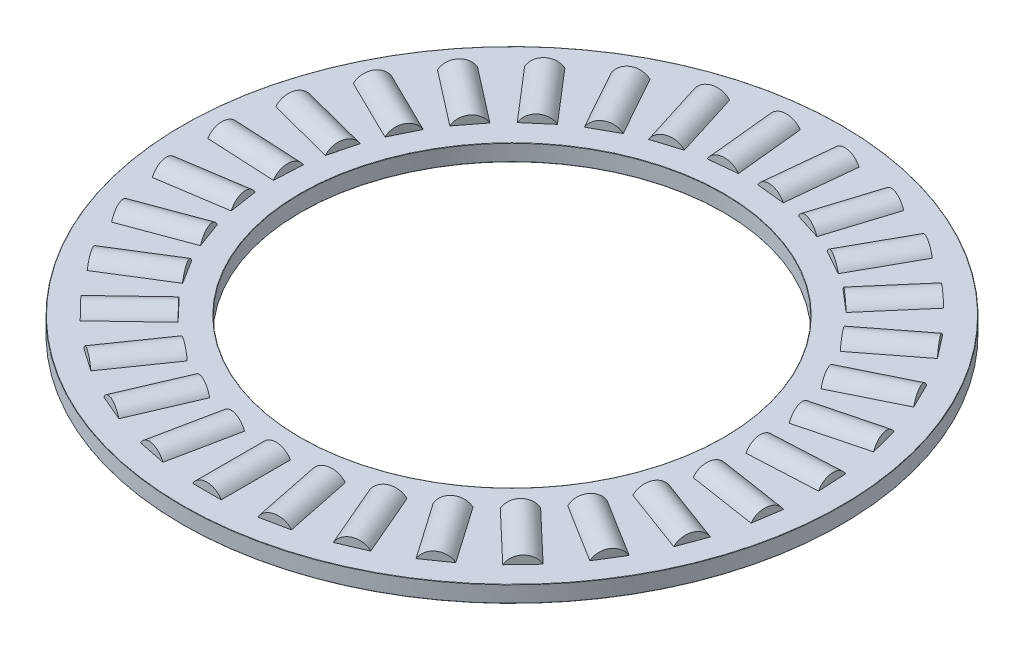
SolidWorks part; units mm, degrees
ref_plane "Front Plane" through (0, 0, 0) normal (0, 0, 1) x (1, 0, 0)
ref_plane "Top Plane" through (0, 0, 0) normal (0, 1, 0) x (1, 0, 0)
ref_plane "Right Plane" through (0, 0, 0) normal (1, 0, 0) x (0, 0, -1)
sketch "Sketch1" plane through (0, 0, 0) normal (1, 0, 0) x (0, 0, -1)
  line L0 (-19.8437, 0) -> (19.8438, 0) construction
  line L1 (0, -0.9922) -> (0, 0.9922) construction
  line L2 (-19.8438, 0.4961) -> (-12.7254, 0.4961)
  line L3 (-19.8438, 0.4961) -> (-19.8438, -0.4961)
  line L4 (-19.8438, -0.4961) -> (-12.7254, -0.4961)
  line L5 (-12.7254, 0.4961) -> (-12.7254, -0.4961)
  line L7 (-16.2846, 0.9922) -> (-16.2846, 0.4961) construction
  line L8 (-18.3682, 0.9922) -> (-14.201, 0.9922) construction
  line L9 (-18.3682, 0.9922) -> (-18.3682, -0.9922) construction
  line L10 (-18.3682, -0.9922) -> (-14.201, -0.9922) construction
  line L11 (-14.201, 0.9922) -> (-14.201, -0.9922) construction
  point P16 (-18.3682, 0)
  dimension "OD" = 39.6875
  dimension "Shaft Dia" = 25.4508
  dimension "Th" = 1.9844
  dimension "D2" = 0.9922
  dimension "D1" = 4.1672
  dimension "D3" = 7.1184
revolve "Revolve1" add sketch "Sketch1" angle 360 about L1
sketch "Sketch3" plane through (0, 0, 0) normal (1, 0, 0) x (0, 0, -1)
  line L0 (-18.3682, 0.9922) -> (-18.3682, -0.9922) construction
  line L1 (-18.3682, 0) -> (-14.201, 0)
  line L2 (-18.3682, 0) -> (-18.3682, 0.9922)
  line L3 (-18.3682, 0.9922) -> (-14.201, 0.9922)
  line L4 (-14.201, 0) -> (-14.201, 0.9922)
revolve "Cut-Revolve1" cut sketch "Sketch3" angle 360 about L1
sketch "Sketch2" plane through (0, 0, 0) normal (1, 0, 0) x (0, 0, -1)
  line L1 (-18.3682, 0) -> (-14.201, 0)
  line L2 (-18.3682, 0) -> (-18.3682, 0.9922)
  line L3 (-18.3682, 0.9922) -> (-14.201, 0.9922)
  line L4 (-14.201, 0) -> (-14.201, 0.9922)
revolve "Revolve2" add sketch "Sketch2" angle 360 about L1
ref_axis "Axis1" through (0, 0.9922, 0) along (0, -1, 0)
pattern_circular "CirPattern1" count 31 every 11.613 about axis through (0, 0.9922, 0) along (0, -1, 0) of bodies 187 411
pattern_circular "CirPattern2" count 31 every 11.613 about axis through (0, 0.9922, 0) along (0, -1, 0) of "Cut-Revolve1"
sketch "Sketch4" plane through (0, 0, 0) normal (1, 0, 0) x (0, 0, -1)
  line L0 (-19.8438, 0.4961) -> (-19.8438, -0.4961) construction
  line L1 (-11.9062, 9.1091) -> (-6.35, 9.1091)
  line L2 (-11.9062, 9.1091) -> (-11.9062, 9.9219)
  line L3 (-11.9062, 9.9219) -> (-6.35, 9.9219)
  line L4 (-6.35, 9.1091) -> (-6.35, 9.9219)
  line L5 (-11.9062, -9.9219) -> (-12.7254, -9.9219)
  line L6 (-11.9062, -9.9219) -> (-11.9062, -9.1091)
  line L7 (-11.9062, -9.1091) -> (-12.7254, -9.1091)
  line L8 (-12.7254, -9.9219) -> (-12.7254, -9.1091)
  line L10 (-12.7254, 0.4961) -> (-12.7254, -0.4961) construction
  line L11 (0, 0) -> (-19.8437, 0) construction
  line L12 (-19.8437, 0) -> (19.8438, 0) construction
  line L13 (0, -0.9922) -> (0, 0.9922) construction
  dimension "Ht" = 19.8438
  dimension "Washer Th" = 0.8128
  dimension "Washer ID" = 12.7
  dimension "Washer OD" = 23.8125
fillet "Fillet2" radius 0.0198 4 edges at (0, -0.4961, -12.7254) (0, 0.4961, -12.7254) (0, -0.4961, -19.8438) (0, 0.4961, -19.8438)
equation "\"D2@Sketch1\"= \"Th@Sketch1\" * .5"
equation "\"Rollers@CirPattern1\"= \"OD@Sketch1\" * 20"
equation "\"Angle@CirPattern1\" = 360/\"Rollers@CirPattern1\""
equation "\"D1@CirPattern2\" = \"Rollers@CirPattern1\""
equation "\"D2@CirPattern2\" = \"Angle@CirPattern1\""
equation "\"Ht@Sketch4\" = \"Th@Sketch1\"*10"
